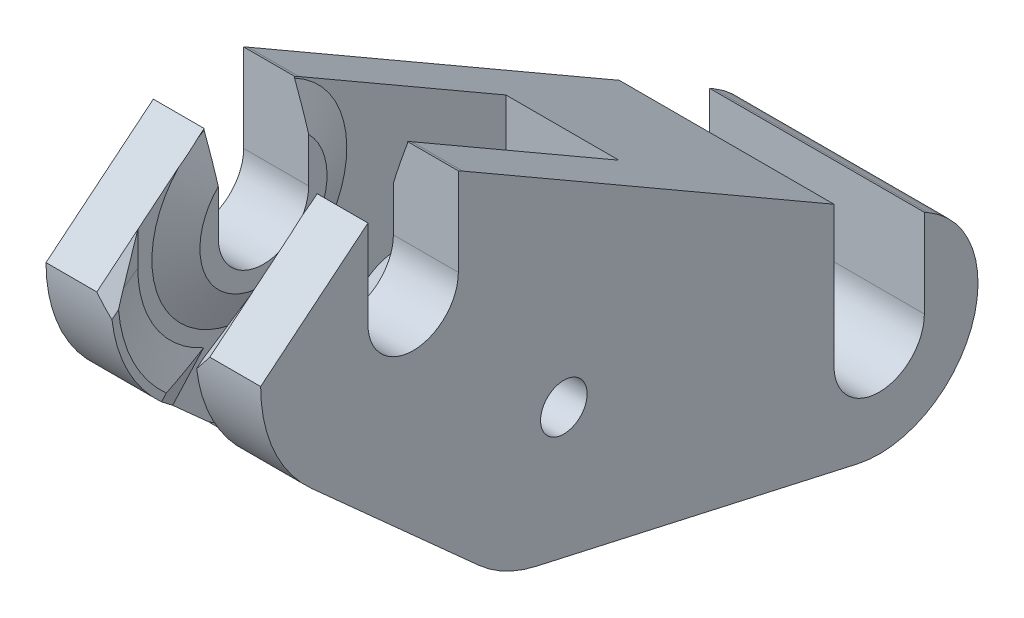
SolidWorks part; units mm, degrees
ref_plane "Front Plane" through (0, 0, 0) normal (0, 0, 1) x (1, 0, 0)
ref_plane "Top Plane" through (0, 0, 0) normal (0, 1, 0) x (1, 0, 0)
ref_plane "Right Plane" through (0, 0, 0) normal (1, 0, 0) x (0, 0, -1)
ref_plane "Plane4" through (15.2, 0, 0) normal (1, 0, 0) x (0, 0, -1)
ref_plane "Plane5" through (7.6, 0, 0) normal (1, 0, 0) x (0, 0, -1)
sketch "Sketch1" plane through (15.2, 0, 0) normal (1, 0, 0) x (0, 0, -1)
  line L0 (3.5235, 220.1706) -> (3.2238, 220.3437)
  line L1 (-32.977, 233.1595) -> (-32.9759, 206.2902) construction
  line L2 (-29.777, 233.1595) -> (-29.777, 239.3852)
  line L4 (-24.2736, 212.3771) -> (-1.5062, 207.2776)
  line L5 (-36.177, 233.1595) -> (-36.177, 239.3852)
  line L6 (3.2238, 214.1083) -> (3.2238, 220.3437)
  line L7 (-3.1762, 214.1083) -> (-3.1762, 224.0384)
  line L8 (-3.1762, 224.0384) -> (-29.4773, 239.2218)
  line L10 (-40.1924, 225.1235) -> (-28.3194, 214.4628)
  line L11 (-36.177, 239.3852) -> (-43.777, 233.1595)
  arc A1 (3.2238, 214.1083) -> (-3.1762, 214.1083) centre (0.0238, 214.1083) cw
  arc A2 (-29.777, 233.1595) -> (-36.177, 233.1595) centre (-32.977, 233.1595) cw
  arc A3 (-1.5062, 207.2776) -> (3.5235, 220.1706) centre (0.0238, 214.1083) ccw
  arc A4 (-29.4773, 239.2218) -> (-29.777, 239.3852) centre (-32.977, 233.1595) ccw
  arc A5 (-43.777, 233.1595) -> (-40.1924, 225.1235) centre (-32.977, 233.1595) ccw
  circle A6 centre (-22.3065, 221.1595) radius 1.65
  arc A7 (-28.3194, 214.4628) -> (-24.2736, 212.3771) centre (-22.3065, 221.1595) ccw
  dimension "D1" = 3.3
  dimension "D2" = 6.4
  dimension "D3" = 7
  dimension "D8" = 9
  dimension "D9" = 21.6
  dimension "D4" = 38.1051
  dimension "D5" = 60
  dimension "D6" = 10.67
  dimension "D7" = 12
extrude "Boss-Extrude1" add sketch "Sketch1" against normal blind 15.2
ref_axis "Axis1" through (0, 214.1083, -0.0238) along (1, 0, 0)
sketch "Sketch4" plane through (7.6, 0, 0) normal (1, 0, 0) x (0, 0, -1)
  line L0 (-39.3964, 223.6179) -> (-26.4931, 214.9367)
  line L1 (-14.8065, 221.1595) -> (-14.8065, 244.6595)
  line L2 (-14.8065, 244.6595) -> (-32.977, 244.6595)
  arc A0 (-26.4931, 214.9367) -> (-14.8065, 221.1595) centre (-22.3065, 221.1595) ccw
  circle A1 centre (-22.3065, 221.1595) radius 1.65 construction
  circle A2 centre (-22.3065, 221.1595) radius 5 construction
  circle A3 centre (-32.977, 233.1595) radius 9.5 construction
  arc A4 (-32.977, 244.6595) -> (-39.3964, 223.6179) centre (-32.977, 233.1595) ccw
  dimension "D1" = 2.5
  dimension "D2" = 19
  dimension "D3" = 10
  dimension "D4" = 2
extrude "Cut-Extrude2" cut sketch "Sketch4" against normal blind 4 and the other way blind 4
sketch "Sketch6" plane through (3.6, 0, 0) normal (1, 0, 0) x (0, 0, -1)
  circle A0 centre (-22.3065, 221.1595) radius 2.6
  circle A1 centre (-22.3065, 221.1595) radius 1.65
  dimension "D1" = 5.2
extrude "Boss-Extrude4" add sketch "Sketch6" along normal blind 2
sketch "Sketch7" plane through (3.6, 0, 0) normal (1, 0, 0) x (0, 0, -1)
  line L0 (-36.177, 233.1595) -> (-36.177, 236.3233)
  line L1 (-43.277, 233.1595) -> (-43.277, 233.5691)
  line L2 (-29.777, 236.3233) -> (-29.777, 233.1595)
  line L3 (-39.8584, 225.4955) -> (-40.1924, 225.1235)
  line L5 (-43.277, 233.5691) -> (-43.777, 233.1595)
  line L6 (-36.177, 239.3852) -> (-43.777, 233.1595) construction
  line L13 (-25.3871, 216.2452) -> (-26.29, 214.8048)
  line L14 (-16.5065, 221.1595) -> (-14.8065, 221.1595)
  arc A0 (-36.177, 233.1595) -> (-29.777, 233.1595) centre (-32.977, 233.1595) ccw
  arc A1 (-36.177, 236.3233) -> (-29.777, 236.3233) centre (-32.977, 233.1595) ccw
  arc A2 (-43.777, 233.1595) -> (-40.1924, 225.1235) centre (-32.977, 233.1595) ccw
  arc A3 (-43.277, 233.1595) -> (-39.8584, 225.4955) centre (-32.977, 233.1595) ccw
  arc A4 (-26.29, 214.8048) -> (-14.8065, 221.1595) centre (-22.3065, 221.1595) ccw
  arc A5 (-25.3871, 216.2452) -> (-16.5065, 221.1595) centre (-22.3065, 221.1595) ccw
  dimension "D1" = 4.5
  dimension "D2" = 10.3
  dimension "D3" = 11.6
  dimension "D4" = 15
extrude "Boss-Extrude5" add sketch "Sketch7" along normal blind 1
chamfer "Chamfer4" distance 2.4 distance2 1 1 edges at (3.6, 228.6595, 32.977) first distance on face at (3.6, 221.1595, 19.7065)
chamfer "Chamfer6" distance 2.4 distance2 1 3 edges at (3.6, 233.3643, 43.277) (3.6, 228.9635, 42.3836) (3.6, 225.3095, 40.0254) first distance on face at (3.6, 221.1595, 19.7065)
mirror "Mirror3" about plane through (7.6, 0, 0) normal (1, 0, 0) of "Boss-Extrude4", "Boss-Extrude5"
chamfer "Chamfer7" distance 1.4 distance2 1 3 edges at (3.6, 216.0847, 19.4983) (3.6, 221.1595, 15.6565) (3.6, 215.525, 25.8386) first distance on face at (3.6, 226.5817, 29.4097)
chamfer "Chamfer8" distance 1.4 distance2 2 1 edges at (3.6, 221.1595, 19.7065) first distance on face at (3.6, 227.7825, 29.8192)
chamfer "Chamfer9" distance 1 distance2 2.4 1 edges at (11.6, 228.6595, 32.977) first distance on face at (11.1, 232.4914, 32.977)
chamfer "Chamfer10" distance 1 distance2 2.4 3 edges at (11.6, 233.3643, 43.277) (11.6, 225.3095, 40.0254) (11.6, 228.9635, 42.3836) first distance on face at (11.1, 233.3643, 43.277) first distance on face at (11.1, 225.3095, 40.0254) first distance on face at (11.1, 229.1455, 41.9757)
chamfer "Chamfer11" distance 2 distance2 1.4 1 edges at (11.6, 221.1595, 19.7065) first distance on face at (9.6, 221.1595, 19.7065)
chamfer "Chamfer12" distance 1 distance2 1.4 3 edges at (11.6, 221.1595, 15.6565) (11.6, 216.0847, 19.4983) (11.6, 215.525, 25.8386) first distance on face at (11.1, 221.1595, 15.6565) first distance on face at (11.1, 217.3935, 20.2225) first distance on face at (11.1, 215.525, 25.8386)
chamfer "Chamfer13" distance 1 distance2 1 2 edges at (10.6, 233.3643, 43.527) (4.6, 233.3643, 43.527)
